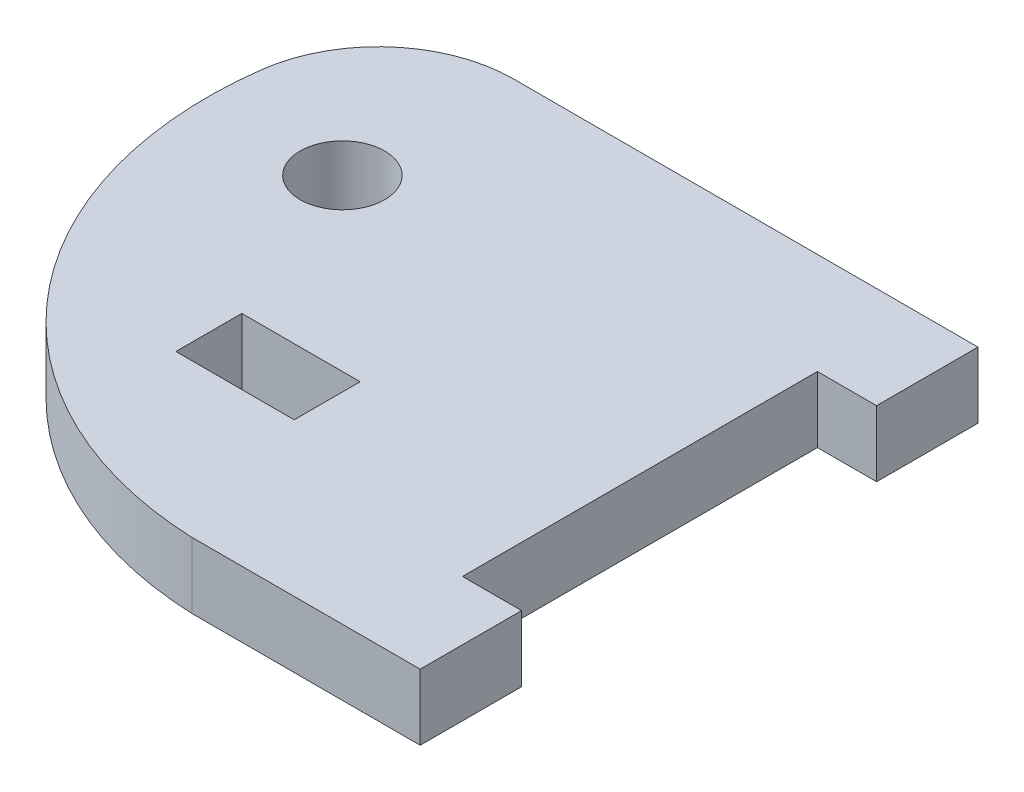
SolidWorks part; units mm, degrees
ref_plane "Front" through (0, 0, 0) normal (0, 0, 1) x (1, 0, 0)
ref_plane "Top" through (0, 0, 0) normal (0, 1, 0) x (1, 0, 0)
ref_plane "Right" through (0, 0, 0) normal (1, 0, 0) x (0, 0, -1)
ref_axis "side-side" through (80.9, 0, 0) along (-1, 0, 0)
ref_axis "up-down" through (0, 50, 0) along (0, -1, 0)
ref_axis "front-back" through (0, 0, -80.9) along (0, 0, 1)
sketch "Sketch1" plane through (0, 0, 0) normal (0, 1, 0) x (1, 0, 0)
  line L0 (30.607, -21.59) -> (30.607, 5.08)
  line L1 (35.56, 0) -> (35.56, -76.5159) construction
  line L2 (35.052, -29.21) -> (17.907, -29.21)
  line L3 (0.1699, 12.7) -> (35.052, 12.7)
  line L5 (30.607, -21.59) -> (35.052, -21.59)
  line L6 (14.097, -12.7635) -> (5.207, -12.7635)
  line L7 (30.607, 5.08) -> (35.052, 5.08)
  line L8 (35.052, 12.7) -> (35.052, 5.08)
  line L9 (14.097, -12.7635) -> (14.097, -17.7165)
  line L10 (35.052, -21.59) -> (35.052, -29.21)
  line L11 (14.097, -17.7165) -> (5.207, -17.7165)
  line L12 (5.207, -12.7635) -> (5.207, -17.7165)
  arc A0 (17.907, -29.21) -> (-9.8996, 3.893) centre (19.0733, 0) cw
  circle A1 centre (0, 0) radius 3.175 construction
  circle A2 centre (0, 0) radius 3.175
  arc A3 (-9.8996, 3.893) -> (0.1699, 12.7) centre (0.1699, 2.54) cw
  dimension "D6" = 10.16
  dimension "D1" = 4.953
  dimension "D2" = 12.7
  dimension "D3" = 41.91
  dimension "D4" = 12.7
  dimension "D5" = 10.16
  dimension "D7" = 0.508
  dimension "D8" = 7.62
  dimension "D9" = 4.953
extrude "Boss-Extrude1" add sketch "Sketch1" along normal mid plane 4.953
